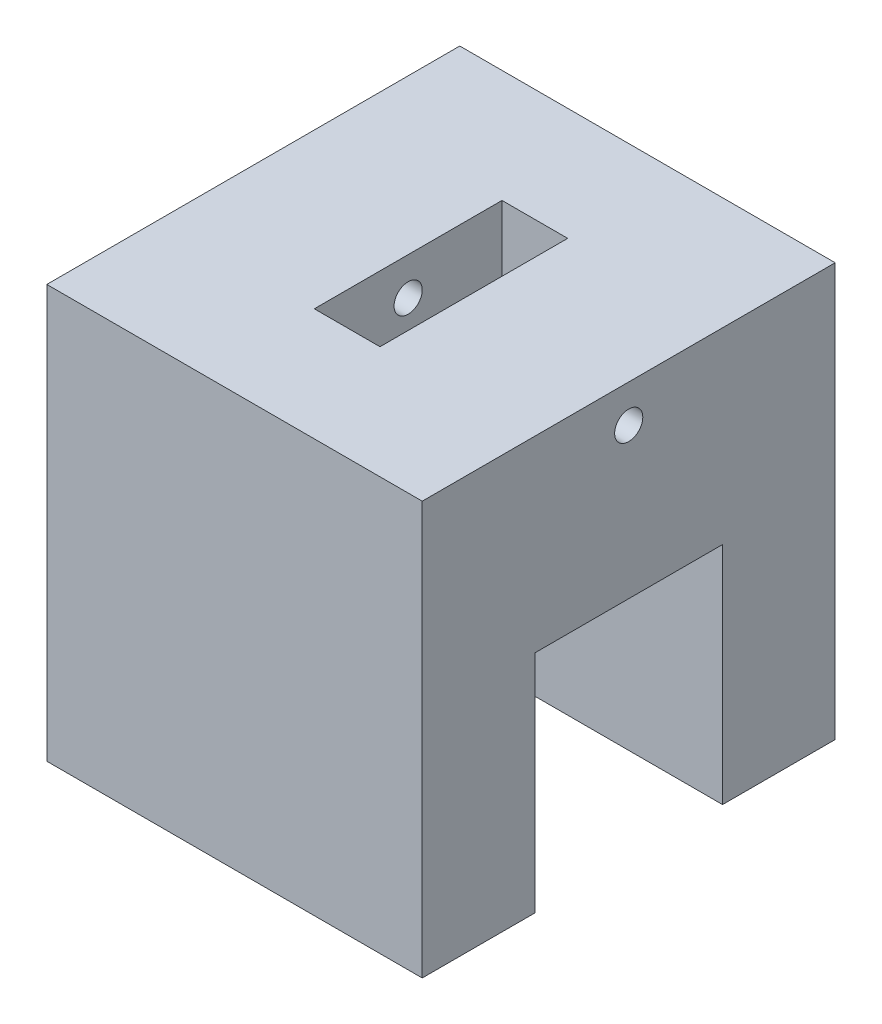
SolidWorks part; units mm, degrees
material "ABS"
ref_plane "Front Plane" through (0, 0, 0) normal (0, 0, 1) x (1, 0, 0)
ref_plane "Top Plane" through (0, 0, 0) normal (0, 1, 0) x (1, 0, 0)
ref_plane "Right Plane" through (0, 0, 0) normal (1, 0, 0) x (0, 0, -1)
sketch "Sketch3" plane through (0, 0, 0) normal (1, 0, 0) x (0, 0, -1)
  line L0 (-110, -120) -> (-50, -120)
  line L1 (-50, -120) -> (-50, 0)
  line L2 (-50, 0) -> (50, 0)
  line L3 (50, 0) -> (50, -120)
  line L4 (50, -120) -> (110, -120)
  line L5 (110, -120) -> (110, 100)
  line L6 (110, 100) -> (-110, 100)
  line L7 (-110, 100) -> (-110, -120)
  circle A0 centre (0, 80) radius 7.5
  point P8 (0, 0)
  dimension "D6" = 110
  dimension "D7" = 15
  dimension "D8" = 20
  dimension "D1" = 220
  dimension "D2" = 220
  dimension "D3" = 120
  dimension "D4" = 60
  dimension "D5" = 60
extrude "Boss-Extrude2" add sketch "Sketch3" along normal blind 100 and the other way blind 100
sketch "Sketch4" plane through (0, 100, 0) normal (0, 1, 0) x (1, 0, 0)
  line L0 (-100, -110) -> (100, -110) construction
  line L1 (-17.5, 50) -> (17.5, 50)
  line L2 (-17.5, 50) -> (-17.5, -50)
  line L3 (-17.5, -50) -> (17.5, -50)
  line L4 (17.5, 50) -> (17.5, -50)
  point P4 (0, -50)
  dimension "D1" = 35
  dimension "D2" = 100
  dimension "D3" = 60
extrude "Cut-Extrude1" cut sketch "Sketch4" against normal blind 60
sketch "Sketch5" plane through (0, 0, 0) normal (0, -1, 0) x (1, 0, 0)
  line L0 (-70, 0) -> (70, 0) construction
  circle A0 centre (-70, 0) radius 7.5
  circle A1 centre (70, 0) radius 7.5
  point P6 (0, 0)
  dimension "D1" = 15
  dimension "D2" = 140
extrude "Cut-Extrude2" cut sketch "Sketch5" against normal blind 60
